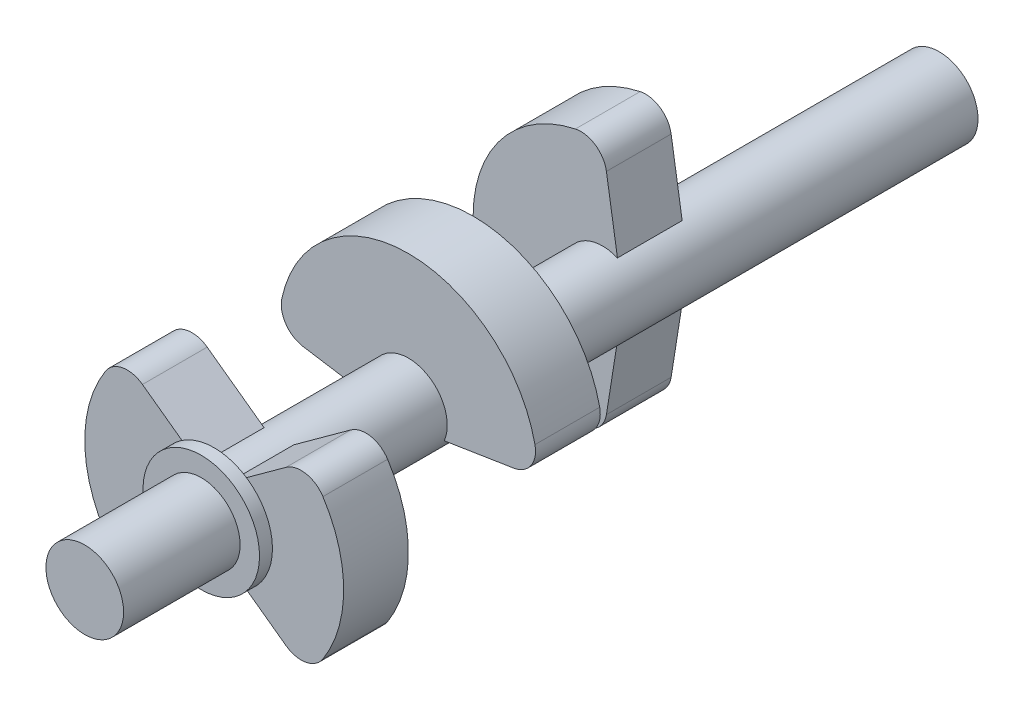
SolidWorks part; units mm, degrees
ref_plane "Спереди" through (0, 0, 0) normal (0, 0, 1) x (1, 0, 0)
ref_plane "Сверху" through (0, 0, 0) normal (0, 1, 0) x (1, 0, 0)
ref_plane "Справа" through (0, 0, 0) normal (1, 0, 0) x (0, 0, -1)
sketch "Эскиз2" plane through (0, 0, 0) normal (0, 0, 1) x (1, 0, 0)
  circle A0 centre (0, 0) radius 1.5
  dimension "D1" = 3
extrude "shaft" add sketch "Эскиз2" along normal blind 33
ref_plane "excentric1plane" through (0, 0, 10.5) normal (0, 0, -1) x (-1, 0, 0)
sketch "Эскиз3" plane through (0, 0, 10.5) normal (0, 0, -1) x (-1, 0, 0)
  line L0 (1.9134, 4.6194) -> (0, 0) construction
  line L1 (0, 5) -> (0, 0) construction
  line L2 (3.5355, 3.5355) -> (0, 0) construction
  line L3 (4.6194, 1.9134) -> (0, 0) construction
  line L4 (5, 0) -> (0, 0) construction
  line L5 (4.6194, -1.9134) -> (0, 0) construction
  line L6 (3.5355, -3.5355) -> (0, 0) construction
  line L7 (1.9134, -4.6194) -> (0, 0) construction
  line L8 (0, -5) -> (0, 0) construction
  line L9 (-1.2555, -3.031) -> (-0.574, -1.3858) construction
  line L10 (-3.5355, -3.5355) -> (0, 0) construction
  line L11 (-4.6194, -1.9134) -> (0, 0) construction
  line L12 (-5, 0) -> (0, 0) construction
  line L13 (-4.6194, 1.9134) -> (0, 0) construction
  line L14 (-3.5355, 3.5355) -> (0, 0) construction
  line L15 (-1.2555, 3.031) -> (-0.574, 1.3858) construction
  line L16 (0, 5) -> (-0.574, 1.3858)
  line L17 (0, -5) -> (-0.574, -1.3858)
  circle A0 centre (0, 0) radius 5
  circle A1 centre (0, 0) radius 1.5
  point P21 (0, 0)
  dimension "D2" = 10
  dimension "D1" = 16
ref_plane "excentric2plane" through (0, 0, 18) normal (0, 0, -1) x (-1, 0, 0)
ref_plane "excentric3plane" through (0, 0, 25.5) normal (0, 0, -1) x (-1, 0, 0)
sketch "excentric2sketch" plane through (0, 0, 18) normal (0, 0, -1) x (-1, 0, 0)
  line L0 (1.9134, 4.6194) -> (0, 0) construction
  line L1 (0, 5) -> (0, 0) construction
  line L2 (3.5355, 3.5355) -> (0, 0) construction
  line L3 (4.6194, 1.9134) -> (0, 0) construction
  line L4 (5, 0) -> (0, 0) construction
  line L5 (3.031, -1.2555) -> (1.3858, -0.574) construction
  line L6 (3.5355, -3.5355) -> (0, 0) construction
  line L7 (1.9134, -4.6194) -> (0, 0) construction
  line L8 (0, -5) -> (0, 0) construction
  line L9 (-1.2555, -3.031) -> (-0.574, -1.3858) construction
  line L10 (-3.5355, -3.5355) -> (0, 0) construction
  line L11 (-3.031, -1.2555) -> (-1.3858, -0.574) construction
  line L12 (-5, 0) -> (0, 0) construction
  line L13 (-4.6194, 1.9134) -> (0, 0) construction
  line L14 (-3.5355, 3.5355) -> (0, 0) construction
  line L15 (-1.2555, 3.031) -> (-0.574, 1.3858) construction
  line L16 (-5, 0) -> (-1.3858, -0.574)
  line L17 (5, 0) -> (1.3858, -0.574)
  circle A0 centre (0, 0) radius 5
  circle A1 centre (0, 0) radius 1.5
  point P21 (0, 0)
  dimension "D2" = 10
  dimension "D1" = 16
sketch "excentric3sketch" plane through (0, 0, 25.5) normal (0, 0, -1) x (-1, 0, 0)
  line L0 (1.9134, 4.6194) -> (0, 0) construction
  line L1 (0, 5) -> (0, 0) construction
  line L2 (3.5355, 3.5355) -> (0, 0) construction
  line L3 (4.6194, 1.9134) -> (0, 0) construction
  line L4 (5, 0) -> (0, 0) construction
  line L5 (4.6194, -1.9134) -> (0, 0) construction
  line L6 (3.5355, -3.5355) -> (0, 0) construction
  line L7 (1.9134, -4.6194) -> (0, 0) construction
  line L8 (0, -5) -> (0, 0) construction
  line L9 (-1.2555, -3.031) -> (-0.574, -1.3858) construction
  line L10 (-3.5355, -3.5355) -> (0, 0) construction
  line L11 (-4.6194, -1.9134) -> (0, 0) construction
  line L12 (-5, 0) -> (0, 0) construction
  line L13 (-4.6194, 1.9134) -> (0, 0) construction
  line L14 (-3.5355, 3.5355) -> (0, 0) construction
  line L15 (-1.2555, 3.031) -> (-0.574, 1.3858) construction
  line L16 (3.5355, 3.5355) -> (0.574, 1.3858)
  line L17 (3.5355, -3.5355) -> (0.574, -1.3858)
  line L18 (-3.5355, -3.5355) -> (-0.574, -1.3858)
  line L19 (-3.5355, 3.5355) -> (-0.574, 1.3858)
  circle A0 centre (0, 0) radius 5
  circle A1 centre (0, 0) radius 1.5
  point P21 (0, 0)
  dimension "D2" = 10
  dimension "D1" = 16
extrude "excentric1" add sketch "Эскиз3" against normal blind 2.5 contours A1 L17 A0 L16 region at (-2.1395, 0, 10.5)
extrude "Бобышка-Вытянуть3" add sketch "excentric2sketch" against normal blind 2.5 contours A1 L17 A0 L16 region at (0, 2.1395, 18)
extrude "Бобышка-Вытянуть4" add sketch "excentric3sketch" against normal blind 2.5 contours A1 L19 A0 L18 | A1 L17 A0 L16 region at (-3.0612, 0, 25.5) region at (3.0612, 0, 25.5)
fillet "Скругление1" radius 1 8 edges at (-3.5355, 3.5355, 26.75) (3.5355, 3.5355, 26.75) (3.5355, -3.5355, 26.75) (-3.5355, -3.5355, 26.75) (-5, 0, 19.25) (5, 0, 19.25) (0, -5, 11.75) (0, 5, 11.75)
sketch "Эскиз7" plane through (0, 0, 28) normal (0, 0, 1) x (1, 0, 0)
  circle A0 centre (0, 0) radius 2.25
  dimension "D1" = 4.5
extrude "Бобышка-Вытянуть5" add sketch "Эскиз7" along normal blind 0.5
